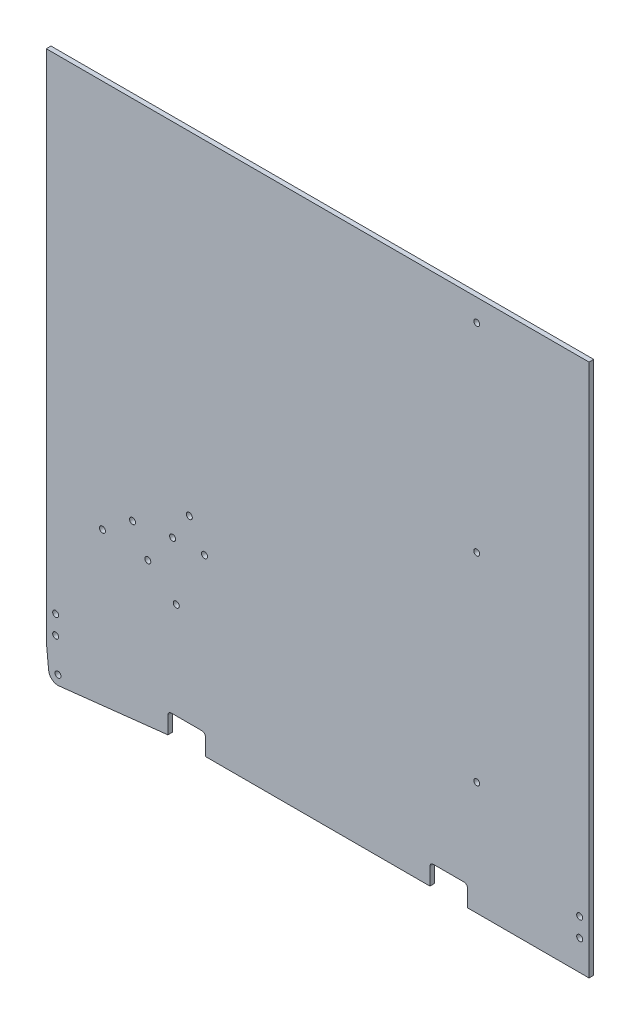
SolidWorks part; units mm, degrees
ref_plane "Front Plane" through (0, 0, 0) normal (0, 0, 1) x (1, 0, 0)
ref_plane "Top Plane" through (0, 0, 0) normal (0, 1, 0) x (1, 0, 0)
ref_plane "Right Plane" through (0, 0, 0) normal (1, 0, 0) x (0, 0, -1)
sketch "Sketch1" plane through (0, 0, 0) normal (0, 0, 1) x (1, 0, 0)
  line L0 (82.55, -20.32) -> (82.55, -6.35)
  line L2 (0, 0) -> (0, 341.63)
  line L3 (0, 341.63) -> (368.3, 341.63)
  line L4 (368.3, -20.32) -> (368.3, 341.63)
  line L5 (82.55, -6.35) -> (107.95, -6.35)
  line L6 (107.95, -6.35) -> (107.95, -20.32)
  line L7 (107.95, -20.32) -> (260.35, -20.32)
  line L8 (260.35, -20.32) -> (260.35, -6.35)
  line L9 (260.35, -6.35) -> (285.75, -6.35)
  line L10 (285.75, -6.35) -> (285.75, -20.32)
  line L11 (285.75, -20.32) -> (368.3, -20.32)
  line L12 (361.95, 12.7) -> (368.3, 12.7) construction
  line L13 (0, 0) -> (6.35, 0) construction
  line L14 (0.0315, -6.9818) -> (1.619, -22.8568)
  line L15 (8.6391, -28.5361) -> (82.55, -20.32)
  line L16 (0, 0) -> (0, -6.35)
  line L17 (85.725, 97.155) -> (82.9754, 95.5675) construction
  line L18 (97.0634, 115.6163) -> (58.5686, 93.3913) construction
  line L19 (97.0634, 115.6163) -> (107.3822, 97.7437) construction
  line L20 (58.5686, 93.3913) -> (68.8873, 75.5187) construction
  line L21 (107.3822, 97.7437) -> (68.8873, 75.5187) construction
  line L22 (97.0634, 115.6163) -> (68.8873, 75.5187) construction
  line L23 (58.5686, 93.3913) -> (107.3822, 97.7437) construction
  line L24 (7.9375, -22.225) -> (88.2169, 59.1366) construction
  line L25 (292.1, 56.63) -> (292.1, 191.63) construction
  line L26 (292.1, 191.63) -> (292.1, 326.63) construction
  circle A0 centre (6.35, 0) radius 2.032
  circle A1 centre (6.35, 12.7) radius 2.032
  circle A2 centre (361.95, 0) radius 2.032
  circle A3 centre (361.95, 12.7) radius 2.032
  arc A5 (1.619, -22.8568) -> (8.6391, -28.5361) centre (7.9375, -22.225) ccw
  circle A6 centre (7.9375, -22.225) radius 2.032
  arc A7 (0, -6.35) -> (0.0315, -6.9818) centre (6.35, -6.35) ccw
  circle A8 centre (38.1, 78.105) radius 2.032
  circle A9 centre (85.725, 97.155) radius 2.032
  circle A10 centre (58.5686, 93.3913) radius 2.032
  circle A11 centre (68.8873, 75.5187) radius 2.032
  circle A12 centre (107.3822, 97.7437) radius 2.032
  circle A13 centre (97.0634, 115.6163) radius 2.032
  circle A14 centre (88.2169, 59.1366) radius 2.032
  circle A15 centre (292.1, 56.63) radius 2
  circle A16 centre (292.1, 191.63) radius 2
  circle A17 centre (292.1, 326.63) radius 2
  dimension "D6" = 4.064
  dimension "D10" = 6.35
  dimension "D11" = 4.064
  dimension "D17" = 38.1
  dimension "D27" = 4
  dimension "D2" = 361.95
  dimension "D3" = 13.97
  dimension "D4" = 25.4
  dimension "D5" = 152.4
  dimension "D7" = 12.7
  dimension "D8" = 6.35
  dimension "D9" = 20.32
  dimension "D12" = 22.225
  dimension "D13" = 1.5875
  dimension "D14" = 82.55
  dimension "D15" = 368.3
  dimension "D16" = 6.35
  dimension "D18" = 98.425
  dimension "D19" = 47.625
  dimension "D20" = 19.05
  dimension "D21" = 3.175
  dimension "D22" = 60
  dimension "D23" = 20.6375
  dimension "D24" = 44.45
  dimension "D25" = 38.1
  dimension "D26" = 114.3
  dimension "D28" = 135
  dimension "D29" = 15
  dimension "D30" = 76.2
extrude "Boss-Extrude1" add sketch "Sketch1" along normal blind 3.175
fillet "Fillet1" radius 2.286 4 edges at (285.75, -6.35, 1.5875) (107.95, -6.35, 1.5875) (260.35, -6.35, 1.5875) (82.55, -6.35, 1.5875)
